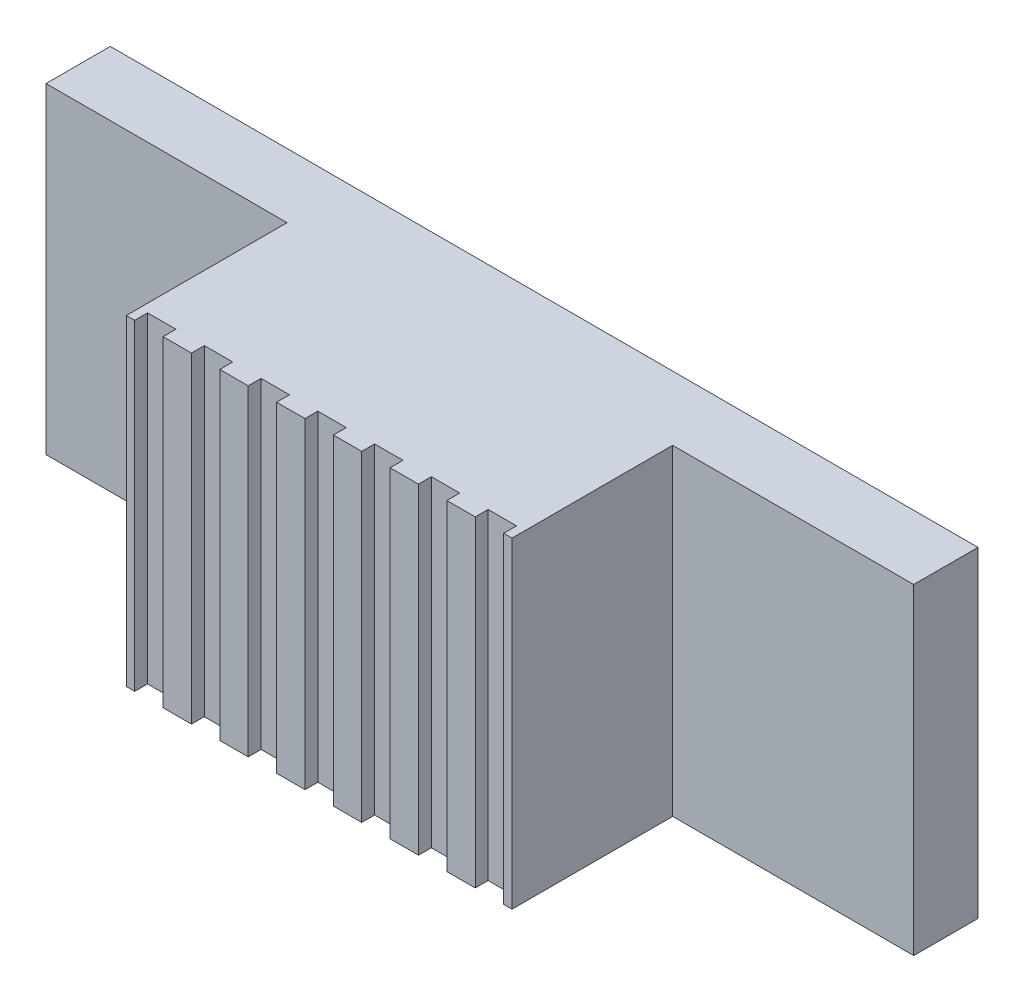
SolidWorks part; units mm, degrees
note: The reader was unsure of these and kept them because the rebuilt part matched: shared geometry of "Sketch1<3>".
ref_plane "Front Plane" through (0, 0, 0) normal (0, 0, 1) x (1, 0, 0)
ref_plane "Top Plane" through (0, 0, 0) normal (0, 1, 0) x (1, 0, 0)
ref_plane "Right Plane" through (0, 0, 0) normal (1, 0, 0) x (0, 0, -1)
sketch "Sketch1" plane through (0, 0, 0) normal (0, 0, 1) x (1, 0, 0)
  line L1 (-3, 2.5) -> (3, 2.5)
  line L2 (-3, 2.5) -> (-3, -2.5)
  line L3 (-3, -2.5) -> (3, -2.5)
  line L4 (3, 2.5) -> (3, -2.5)
  line L5 (-3, 2.5) -> (3, -2.5) construction
  line L6 (-3, -2.5) -> (3, 2.5) construction
  line L7 (-6.75, 2.5) -> (6.75, 2.5)
  line L8 (-6.75, 2.5) -> (-6.75, -2.5)
  line L9 (-6.75, -2.5) -> (6.75, -2.5)
  line L10 (6.75, 2.5) -> (6.75, -2.5)
  line L11 (-6.75, 2.5) -> (6.75, -2.5) construction
  line L12 (-6.75, -2.5) -> (6.75, 2.5) construction
  point P0 (0, 0)
  point P6 (0, 0)
  dimension "D1" = 5
  dimension "D2" = 6
  dimension "D3" = 13.5
extrude "Boss-Extrude1" add sketch "Sketch1" along normal blind 3.5 contours L4 L1 L2 L3
extrude "Boss-Extrude2" add sketch "Sketch1<3>" along normal blind 1 contours L8 L9 L2 L7 | L10 L7 L4 L9
sketch "Sketch1<3>" plane through (0, 0, 0) normal (0, 0, 1) x (1, 0, 0) same geometry as "Sketch1"
sketch "Sketch2" plane through (0, 0, 0) normal (0, 0, -1) x (-1, 0, 0)
  line L0 (6.75, -2.5) -> (-6.75, -2.5) construction
  line L1 (-1.05, 2.5) -> (1.05, 2.5)
  line L2 (-1.05, 2.5) -> (-1.05, -2.5)
  line L3 (-1.05, -2.5) -> (1.05, -2.5)
  line L4 (1.05, 2.5) -> (1.05, -2.5)
  line L5 (-1.05, 2.5) -> (1.05, -2.5) construction
  line L6 (-1.05, -2.5) -> (1.05, 2.5) construction
  line L7 (-1.05, 1.5) -> (1.05, 1.5)
  line L8 (-1.05, -1.5) -> (1.05, -1.5)
  point P0 (0, 0)
  line M2 (6.75, 2.5) -> (-6.75, 2.5)
  line M4 (-6.75, -2.5) -> (6.75, -2.5)
  dimension "D1" = 2.1
  dimension "D2" = 1
  dimension "D3" = 1
extrude "Cut-Extrude1" cut sketch "Sketch2" against normal offset from surface (2.5 mm away) 1 contours L4 L2 M2 M4
sketch "Sketch3" plane through (0, 0, 3.5) normal (0, 0, 1) x (1, 0, 0)
  line L0 (-3, 2.5) -> (3, 2.5) construction
  line L1 (-2.8699, 2.5) -> (-2.4284, 2.5)
  line L2 (-2.8699, 2.5) -> (-2.8699, -2.5)
  line L3 (-2.8699, -2.5) -> (-2.4284, -2.5)
  line L4 (-2.4284, 2.5) -> (-2.4284, -2.5)
  line L5 (-3, -2.5) -> (3, -2.5) construction
  line L6 (-3, 1.8649) -> (-2.8699, 1.8649) construction
  line L7 (-3, 2.5) -> (-3, -2.5) construction
  line L8 (-1.9869, 2.5) -> (-1.9869, -2.5)
  line L9 (-1.9869, 2.5) -> (-1.5453, 2.5)
  line L10 (-1.5453, 2.5) -> (-1.5453, -2.5)
  line L11 (-1.9869, -2.5) -> (-1.5453, -2.5)
  line L12 (-1.1038, 2.5) -> (-1.1038, -2.5)
  line L13 (-1.1038, 2.5) -> (-0.6623, 2.5)
  line L14 (-0.6623, 2.5) -> (-0.6623, -2.5)
  line L15 (-1.1038, -2.5) -> (-0.6623, -2.5)
  line L16 (-0.2208, 2.5) -> (-0.2208, -2.5)
  line L17 (-0.2208, 2.5) -> (0.2208, 2.5)
  line L18 (0.2208, 2.5) -> (0.2208, -2.5)
  line L19 (-0.2208, -2.5) -> (0.2208, -2.5)
  line L20 (0.6623, 2.5) -> (0.6623, -2.5)
  line L21 (0.6623, 2.5) -> (1.1038, 2.5)
  line L22 (1.1038, 2.5) -> (1.1038, -2.5)
  line L23 (0.6623, -2.5) -> (1.1038, -2.5)
  line L24 (1.5453, 2.5) -> (1.5453, -2.5)
  line L25 (1.5453, 2.5) -> (1.9869, 2.5)
  line L26 (1.9869, 2.5) -> (1.9869, -2.5)
  line L27 (1.5453, -2.5) -> (1.9869, -2.5)
  line L28 (2.4284, 2.5) -> (2.4284, -2.5)
  line L29 (2.4284, 2.5) -> (2.8699, 2.5)
  line L30 (2.8699, 2.5) -> (2.8699, -2.5)
  line L31 (2.4284, -2.5) -> (2.8699, -2.5)
  line L32 (2.8699, 1.617) -> (3, 1.617) construction
  line L33 (3, 2.5) -> (3, -2.5) construction
  line L34 (-2.8699, 1.4813) -> (-2.4284, 1.4813) construction
  line L35 (-2.4284, 1.4813) -> (-1.9869, 1.4813) construction
  dimension "D1" = 7
extrude "Cut-Extrude2" cut sketch "Sketch3" against normal blind 0.2
